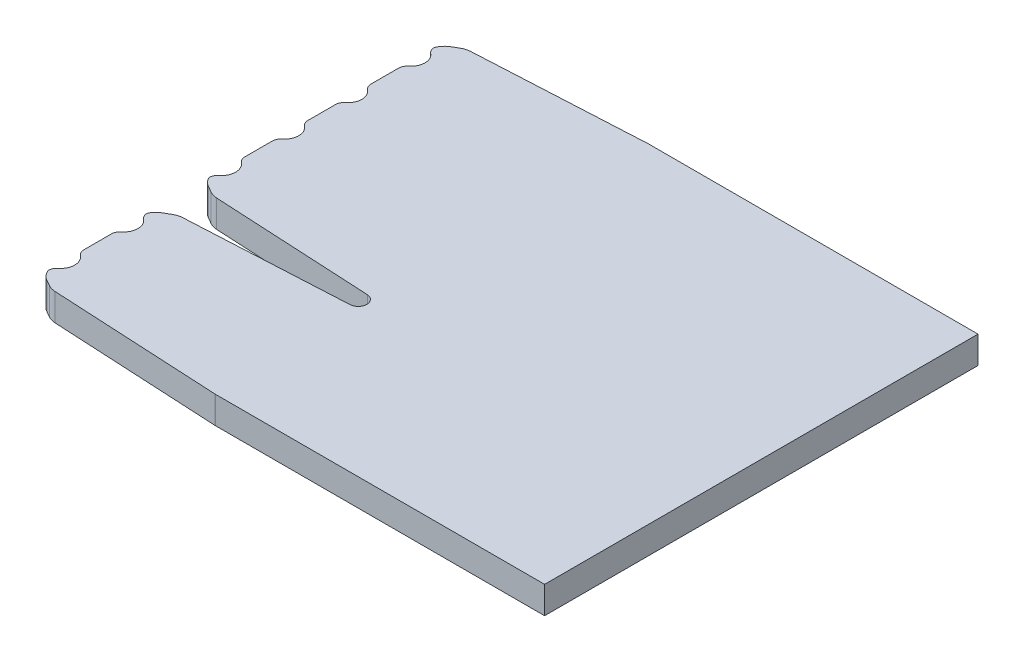
SolidWorks part; units mm, degrees
ref_plane "Front Plane" through (0, 0, 0) normal (0, 0, 1) x (1, 0, 0)
ref_plane "Top Plane" through (0, 0, 0) normal (0, 1, 0) x (1, 0, 0)
ref_plane "Right Plane" through (0, 0, 0) normal (1, 0, 0) x (0, 0, -1)
sketch "Sketch1" plane through (0, 0, 0) normal (0, 1, 0) x (1, 0, 0)
  line L0 (15, 0) -> (15, -12.5) construction
  line L1 (15, 0) -> (0, 0) construction
  line L2 (10, -12.5) -> (10, 12.5) construction
  line L3 (30, -12.5) -> (0, -12.5)
  line L4 (30, -12.5) -> (30, 12.5)
  line L5 (30, 12.5) -> (0, 12.5)
  line L6 (0, -12.5) -> (0, 12.5)
  line L7 (10, -10.1) -> (0, -10.1) construction
  line L8 (10, -6.46) -> (0, -6.46) construction
  line L9 (10, -0.82) -> (0, -0.82) construction
  line L10 (10, 2.82) -> (0, 2.82) construction
  line L11 (10, 6.46) -> (0, 6.46) construction
  line L12 (10, 10.1) -> (0, 10.1) construction
  dimension "D1" = 30
extrude "Boss-Extrude1" add sketch "Sketch1" along normal blind 1.57
sketch "Sketch2" plane through (0, 0, 0) normal (0, 1, 0) x (1, 0, 0)
  line L0 (11, -12.5) -> (11, 12.5) construction
  line L1 (0, 12.5) -> (0, -12.5) construction
  line L2 (11, -10.1) -> (0, -10.1) construction
  line L3 (11, -6.46) -> (0, -6.46) construction
  line L4 (11, -0.82) -> (0, -0.82) construction
  line L5 (11, 2.82) -> (0, 2.82) construction
  line L6 (11, 6.46) -> (0, 6.46) construction
  line L7 (11, 10.1) -> (0, 10.1) construction
  line L8 (10, -12.5) -> (10, 12.5) construction
  line L9 (11, -10.85) -> (0, -10.85)
  line L10 (11, -10.85) -> (11, -9.35)
  line L11 (11, -9.35) -> (0, -9.35)
  line L12 (0, -10.85) -> (0, -9.35)
  line L13 (11, -7.21) -> (0, -7.21)
  line L14 (11, -7.21) -> (11, -5.71)
  line L15 (11, -5.71) -> (0, -5.71)
  line L16 (0, -7.21) -> (0, -5.71)
  line L17 (11, -1.57) -> (0, -1.57)
  line L18 (11, -1.57) -> (11, -0.07)
  line L19 (11, -0.07) -> (0, -0.07)
  line L20 (0, -1.57) -> (0, -0.07)
  line L21 (0, 3.57) -> (11, 3.57)
  line L22 (0, 3.57) -> (0, 2.07)
  line L23 (0, 2.07) -> (11, 2.07)
  line L24 (11, 3.57) -> (11, 2.07)
  line L25 (11, 5.71) -> (0, 5.71)
  line L26 (11, 5.71) -> (11, 7.21)
  line L27 (11, 7.21) -> (0, 7.21)
  line L28 (0, 5.71) -> (0, 7.21)
  line L29 (11, 9.35) -> (0, 9.35)
  line L30 (11, 9.35) -> (11, 10.85)
  line L31 (11, 10.85) -> (0, 10.85)
  line L32 (0, 9.35) -> (0, 10.85)
  line L33 (30, 12.5) -> (0, 12.5) construction
  line L34 (30, -12.5) -> (0, -12.5) construction
  dimension "D1" = 1.5
  dimension "D2" = 1
sketch "Sketch3" plane through (0, 0, 0) normal (0, 1, 0) x (1, 0, 0)
  line L0 (10.4134, -4.1393) -> (1, -4.6326)
  line L1 (0, -4.6326) -> (11, -4.6326) construction
  line L2 (1, -4.6326) -> (0, -5.21)
  line L3 (0, -2.6474) -> (11, -2.6474) construction
  line L4 (11, -4.6326) -> (11, -2.6474) construction
  line L5 (11, -12.5) -> (11, 12.5) construction
  line L6 (11, -5.71) -> (0, -5.71) construction
  line L7 (11, -1.57) -> (0, -1.57) construction
  line L8 (11, -3.64) -> (0, -3.64) construction
  line L9 (1, -4.6326) -> (11, -4.1086) construction
  line L10 (11, -4.1086) -> (11, -3.1714) construction
  line L11 (11, -3.1714) -> (1, -2.6474) construction
  line L12 (1, -12.5) -> (1, 12.5) construction
  line L13 (0, 12.5) -> (0, -12.5) construction
  line L14 (30, -12.5) -> (0, -12.5) construction
  line L15 (30, 12.5) -> (0, 12.5) construction
  line L16 (0, -5.21) -> (0, -2.07)
  line L17 (0, -2.07) -> (1, -2.6474)
  line L18 (11, 12.5) -> (1, 11.9759)
  line L19 (1, 11.9759) -> (0, 11.3986)
  line L20 (0, 11.3986) -> (0, 12.5)
  line L21 (0, 12.5) -> (11, 12.5)
  line L22 (11, -12.5) -> (0, -12.5)
  line L23 (0, -12.5) -> (0, -11.3986)
  line L24 (0, -11.3986) -> (1, -11.9759)
  line L25 (1, -11.9759) -> (11, -12.5)
  line L26 (10.4134, -3.1407) -> (1, -2.6474)
  arc A0 (10.4134, -4.1393) -> (10.4134, -3.1407) centre (10.3872, -3.64) ccw
  dimension "D6" = 1
  dimension "D1" = 0.5
  dimension "D2" = 30
  dimension "D3" = 1
  dimension "D4" = 3
  dimension "D5" = 3.14
extrude "Cut-Extrude1" cut sketch "Sketch3" along normal through all
extrude "Boss-Extrude2" add sketch "Sketch2" against normal blind 0.05
sketch "Sketch4" plane through (0, 0, 0) normal (0, 1, 0) x (1, 0, 0)
  line L0 (0.5, -12.5) -> (-0.3125, -12.5) construction
  line L1 (-0.3125, -10.1) -> (-0.3125, -12.5) construction
  line L2 (-0.3125, 12.5) -> (0.5, 12.5) construction
  line L3 (0.5, 12.5) -> (0.5, -12.5) construction
  line L4 (30, -12.5) -> (0, -12.5) construction
  line L5 (30, 12.5) -> (0, 12.5) construction
  line L6 (0, -12.5) -> (0, 12.5) construction
  line L7 (0.5, 10.1) -> (-0.3125, 10.1) construction
  line L8 (0.5, 6.46) -> (-0.3125, 6.46) construction
  line L9 (0.5, 2.82) -> (-0.3125, 2.82) construction
  line L10 (0.5, -0.82) -> (-0.3125, -0.82) construction
  line L11 (0.5, -6.46) -> (-0.3125, -6.46) construction
  line L12 (0.5, -10.1) -> (-0.3125, -10.1) construction
  line L13 (10, -10.1) -> (0, -10.1) construction
  line L14 (10, -6.46) -> (0, -6.46) construction
  line L15 (10, -0.82) -> (0, -0.82) construction
  line L16 (10, 2.82) -> (0, 2.82) construction
  line L17 (10, 6.46) -> (0, 6.46) construction
  line L18 (10, 10.1) -> (0, 10.1) construction
  line L19 (0.5, -10.85) -> (0, -10.85) construction
  line L20 (0.5, -9.35) -> (0, -9.35) construction
  line L21 (11, -9.35) -> (0, -9.35) construction
  line L22 (11, -10.85) -> (0, -10.85) construction
  line L23 (-0.3125, -10.1) -> (-0.3125, -6.46) construction
  line L24 (-0.3125, -6.46) -> (-0.3125, -0.82) construction
  line L25 (-0.3125, -0.82) -> (-0.3125, 2.82) construction
  line L26 (-0.3125, 2.82) -> (-0.3125, 6.46) construction
  line L27 (-0.3125, 6.46) -> (-0.3125, 10.1) construction
  line L28 (-0.3125, 10.1) -> (-0.3125, 12.5) construction
  line L29 (0, -11.1308) -> (0, -9.0692)
  line L30 (-0.3125, -8.28) -> (0.5, -8.28) construction
  line L31 (0, -5.4292) -> (0, -7.4908)
  line L32 (-0.3125, -3.64) -> (0.5, -3.64) construction
  line L33 (-0.3125, 1) -> (0.5, 1) construction
  line L34 (-0.3125, 4.64) -> (0.5, 4.64) construction
  line L35 (-0.3125, 8.28) -> (0.5, 8.28) construction
  line L36 (0, -1.8508) -> (0, 0.2108)
  line L37 (0, 3.8508) -> (0, 1.7892)
  line L38 (0, 5.4292) -> (0, 7.4908)
  line L39 (0, 11.1308) -> (0, 9.0692)
  circle A0 centre (-0.3125, -10.1) radius 0.8125 construction
  circle A1 centre (0.5, -11.1308) radius 0.5 construction
  circle A2 centre (0.5, -9.0692) radius 0.5 construction
  arc A3 (0.1905, -10.7381) -> (0.1905, -9.4619) centre (-0.3125, -10.1) ccw
  arc A4 (0, -9.0692) -> (0.1905, -9.4619) centre (0.5, -9.0692) ccw
  arc A5 (0.1905, -10.7381) -> (0, -11.1308) centre (0.5, -11.1308) ccw
  arc A6 (0.1905, -5.8219) -> (0, -5.4292) centre (0.5, -5.4292) cw
  arc A7 (0, -7.4908) -> (0.1905, -7.0981) centre (0.5, -7.4908) cw
  arc A8 (0.1905, -5.8219) -> (0.1905, -7.0981) centre (-0.3125, -6.46) cw
  arc A9 (0.1905, -1.4581) -> (0, -1.8508) centre (0.5, -1.8508) ccw
  arc A10 (0.1905, -1.4581) -> (0.1905, -0.1819) centre (-0.3125, -0.82) ccw
  arc A11 (0, 0.2108) -> (0.1905, -0.1819) centre (0.5, 0.2108) ccw
  arc A12 (0.1905, 3.4581) -> (0, 3.8508) centre (0.5, 3.8508) cw
  arc A13 (0.1905, 3.4581) -> (0.1905, 2.1819) centre (-0.3125, 2.82) cw
  arc A14 (0, 1.7892) -> (0.1905, 2.1819) centre (0.5, 1.7892) cw
  arc A15 (0.1905, 5.8219) -> (0, 5.4292) centre (0.5, 5.4292) ccw
  arc A16 (0, 7.4908) -> (0.1905, 7.0981) centre (0.5, 7.4908) ccw
  arc A17 (0.1905, 5.8219) -> (0.1905, 7.0981) centre (-0.3125, 6.46) ccw
  arc A18 (0.1905, 10.7381) -> (0, 11.1308) centre (0.5, 11.1308) cw
  arc A19 (0, 9.0692) -> (0.1905, 9.4619) centre (0.5, 9.0692) cw
  arc A20 (0.1905, 10.7381) -> (0.1905, 9.4619) centre (-0.3125, 10.1) cw
  dimension "D2" = 1
  dimension "D1" = 0.5
extrude "Cut-Extrude2" cut sketch "Sketch4" along normal through all and the other way through all
fillet "Fillet1" radius 1 10 edges at (1, 0.785, -11.9759) (0, 0.785, -11.3986) (0, 0.785, 5.21) (0, 0.785, 2.07) (0, 0.785, 11.3986) (1, 0.785, 11.9759) (11, 0.785, -12.5) (11, 0.785, 12.5) (1, 0.785, 4.6326) (1, 0.785, 2.6474)
sketch "Sketch5" plane through (0, 0, 0) normal (0, 1, 0) x (1, 0, 0)
  line L0 (10, -4.161) -> (10, -3.119) construction
  line L1 (10, -3.119) -> (0, -2.5949) construction
  line L2 (0, -2.5949) -> (0, -4.6851) construction
  line L3 (0, -4.6851) -> (10, -4.161) construction
  line L4 (10, -12.5) -> (10, 12.5) construction
  line L5 (10.4134, -4.1393) -> (1, -4.6326) construction
  line L6 (10.4134, -3.1407) -> (1, -2.6474) construction
  line L7 (0, 12.5) -> (0, -12.5) construction
  line L8 (0, -3.64) -> (10, -3.64) construction
  line L9 (9, -3.913) -> (9, -3.367)
  line L10 (9, -3.367) -> (0, -2.8954)
  line L11 (0, -2.8954) -> (0, -4.3846)
  line L12 (0, -4.3846) -> (9, -3.913)
  dimension "D1" = 0.3
  dimension "D2" = 1
  dimension "D3" = 0.546
